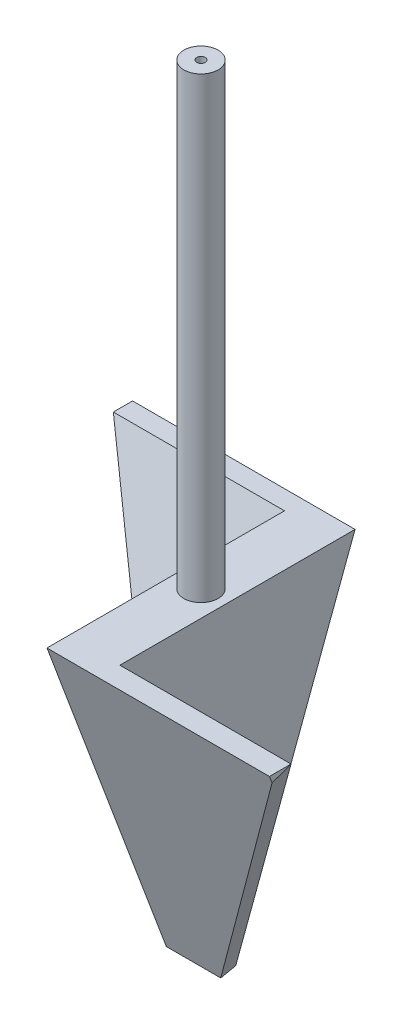
SolidWorks part; units mm, degrees
ref_plane "前视基准面" through (0, 0, 0) normal (0, 0, 1) x (1, 0, 0)
ref_plane "上视基准面" through (0, 0, 0) normal (0, 1, 0) x (1, 0, 0)
ref_plane "右视基准面" through (0, 0, 0) normal (1, 0, 0) x (0, 0, -1)
sketch "草图1" plane through (0, 0, 0) normal (0, 1, 0) x (1, 0, 0)
  circle A0 centre (0, 0) radius 0.5
  dimension "D1" = 1
extrude "凸台-拉伸1" add sketch "草图1" along normal blind 92
shell "抽壳1" thickness 1.5 removed face at (0, 92, 0.5) outward yes
sketch "草图2" plane through (0, 0, 0) normal (0, 1, 0) x (1, 0, 0)
  circle A0 centre (0, 0) radius 1
extrude "凸台-拉伸2" add sketch "草图2" along normal blind 86
sketch "草图5" plane through (0, 0, 0) normal (1, 0, 0) x (0, 0, -1)
  line L1 (-2, -1.5) -> (2, -1.5) construction
  line L7 (0, 38.5) -> (-15, 38.5)
  line L8 (0, 38.5) -> (15, 38.5)
  line L9 (-15, 38.5) -> (0, -1.5)
  line L10 (15, 38.5) -> (0, -1.5)
extrude "凸台-拉伸4" add sketch "草图5" along normal blind 3 and the other way blind 3
sketch "草图6" plane through (0, 0, 0) normal (1, 0, 0) x (0, 0, -1)
  line L6 (0, -1.5) -> (-2.8671, -1.5)
  line L7 (-2, -1.5) -> (0, -1.5) construction
  line L8 (-2.8671, -1.5) -> (-2.8671, 6.1456)
  line L9 (-15, 38.5) -> (0, -1.5) construction
  line L10 (-2, 3.8333) -> (0, -1.5) construction
  line L11 (-2.8671, 6.1456) -> (0, -1.5)
  line L12 (0, -1.5) -> (2.8078, -1.5)
  line L13 (0, -1.5) -> (2, -1.5) construction
  line L14 (2.8078, -1.5) -> (2.8078, 5.9876)
  line L15 (0, -1.5) -> (15, 38.5) construction
  line L16 (0, -1.5) -> (2, 3.8333) construction
  line L17 (2.8078, 5.9876) -> (0, -1.5)
extrude "切除-拉伸1" cut sketch "草图6" against normal blind 3 and the other way blind 3 contours L6 | L6 L8 L11 | L12 L14 L17 region at (0, 1.0485, 1.9114)
sketch "草图8" plane through (0, 0, 0) normal (1, 0, 0) x (0, 0, -1)
  line L0 (0, -1.5) -> (-1.0557, 1.3153)
  line L1 (-15, 38.5) -> (0, -1.5) construction
  line L2 (-1.0557, 1.3153) -> (1.0557, 1.3153)
  line L3 (0, -1.5) -> (15, 38.5) construction
  line L4 (1.0557, 1.3153) -> (0, -1.5)
extrude "切除-拉伸2" cut sketch "草图8" against normal blind 10 and the other way blind 10
ref_plane "基准面1" through (3, 0, 0) normal (1, 0, 0) x (0, 0, -1)
sketch "草图12" plane through (3, 0, 0) normal (1, 0, 0) x (0, 0, -1)
  line L0 (1.0557, 1.3153) -> (-12.4798, 38.5)
  line L1 (15, 38.5) -> (-15, 38.5) construction
  line L2 (-12.4798, 38.5) -> (-15, 38.5)
  line L3 (-15, 38.5) -> (-1.0557, 1.3153)
  line L4 (-1.0557, 1.3153) -> (1.0557, 1.3153)
extrude "凸台-拉伸6" add sketch "草图12" along normal blind 20
sketch "草图14" plane through (0, 0.4932, -1.355) normal (0, 0.3421, -0.9397) x (-1, 0, 0)
  line L0 (-23, 40.4465) -> (-3, 0.8748)
  line L1 (-3, 15.1139) -> (-3, -15.1139) construction
  line L2 (-23, 0.8748) -> (-3, 0.8748) construction
  line L3 (-3, 0.8748) -> (-23, 0.8748)
  line L4 (-23, 0.8748) -> (-23, 40.4465)
extrude "切除-拉伸6" cut sketch "草图14" against normal blind 15
sketch "草图15" plane through (-3, 0, 0) normal (-1, 0, 0) x (0, 0, 1)
  line L0 (1.0557, 1.3153) -> (-12.7565, 38.5)
  line L1 (-15, 38.5) -> (15, 38.5) construction
  line L2 (-12.7565, 38.5) -> (-15, 38.5)
  line L3 (-15, 38.5) -> (-1.0557, 1.3153)
  line L4 (-1.0557, 1.3153) -> (1.0557, 1.3153)
extrude "凸台-拉伸7" add sketch "草图15" along normal blind 20
sketch "草图16" plane through (0, 0.5041, 1.3571) normal (0, 0.3482, 0.9374) x (1, 0, 0)
  line L0 (-3, 0.8654) -> (-23, 40.5325)
  line L1 (-23, 40.5325) -> (-23, 0.8654)
  line L2 (-23, 0.8654) -> (-3, 0.8654)
extrude "切除-拉伸7" cut sketch "草图16" against normal blind 20
